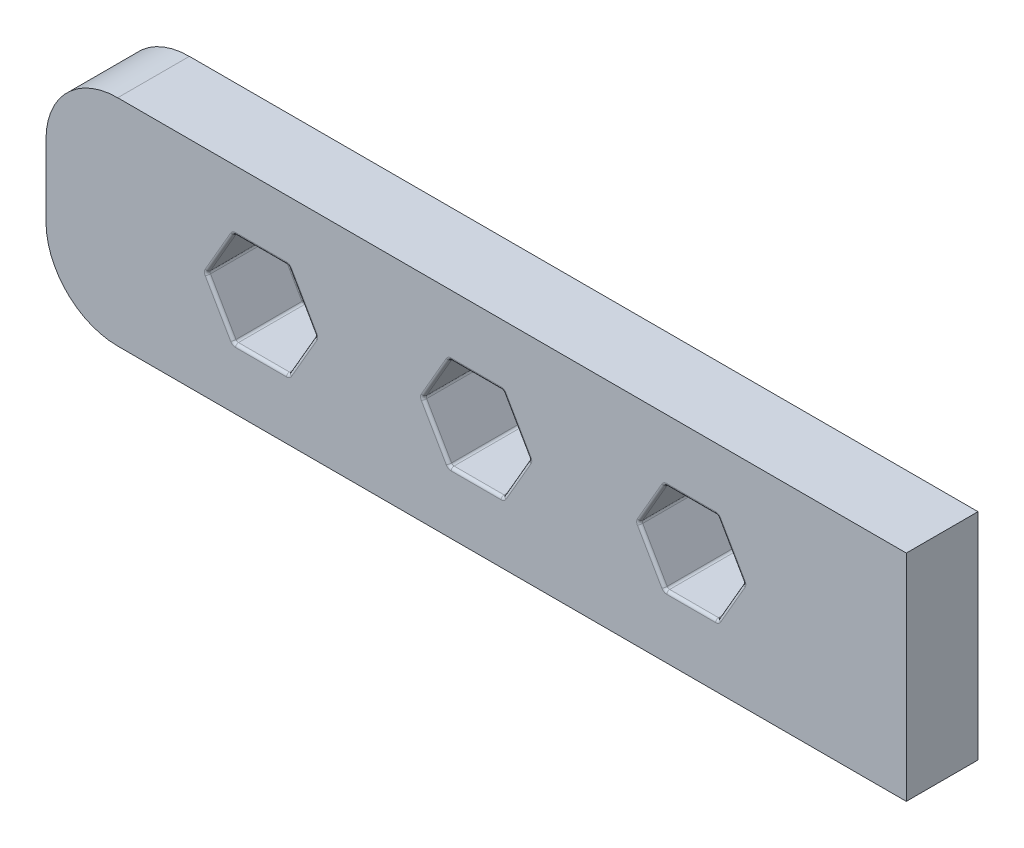
SolidWorks part; units mm, degrees
ref_plane "Front Plane" through (0, 0, 0) normal (0, 0, 1) x (1, 0, 0)
ref_plane "Top Plane" through (0, 0, 0) normal (0, 1, 0) x (1, 0, 0)
ref_plane "Right Plane" through (0, 0, 0) normal (1, 0, 0) x (0, 0, -1)
sketch "Sketch1" plane through (0, 0, 0) normal (0, 0, 1) x (1, 0, 0)
  line L1 (-25, -7.5) -> (30, -7.5)
  line L2 (-30, -2.5) -> (-30, 2.5)
  line L3 (-25, 7.5) -> (30, 7.5)
  line L4 (30, -7.5) -> (30, 7.5)
  line L5 (-30, -7.5) -> (30, 7.5) construction
  line L6 (-30, 7.5) -> (30, -7.5) construction
  arc A0 (-25, -7.5) -> (-30, -2.5) centre (-25, -2.5) cw
  arc A1 (-30, 2.5) -> (-25, 7.5) centre (-25, 2.5) cw
  point P0 (0, 0)
  dimension "D1" = 5
  dimension "D2" = 55
  dimension "D3" = 15
extrude "Boss-Extrude1" add sketch "Sketch1" along normal blind 5
sketch "Sketch2" plane through (0, 0, 0) normal (0, 0, 1) x (1, 0, 0)
  line L1 (-11.2184, 0) -> (-13.1092, 3.275)
  line L2 (-13.1092, 3.275) -> (-16.8908, 3.275)
  line L3 (-16.8908, 3.275) -> (-18.7816, 0)
  line L4 (-18.7816, 0) -> (-16.8908, -3.275)
  line L5 (-16.8908, -3.275) -> (-13.1092, -3.275)
  line L6 (-13.1092, -3.275) -> (-11.2184, 0)
  line L7 (3.7095, 0) -> (1.8547, 3.2125)
  line L8 (1.8547, 3.2125) -> (-1.8547, 3.2125)
  line L9 (-1.8547, 3.2125) -> (-3.7095, 0)
  line L10 (-3.7095, 0) -> (-1.8547, -3.2125)
  line L11 (-1.8547, -3.2125) -> (1.8547, -3.2125)
  line L12 (1.8547, -3.2125) -> (3.7095, 0)
  line L13 (18.6373, 0) -> (16.8187, 3.15)
  line L14 (16.8187, 3.15) -> (13.1813, 3.15)
  line L15 (13.1813, 3.15) -> (11.3627, 0)
  line L16 (11.3627, 0) -> (13.1813, -3.15)
  line L17 (13.1813, -3.15) -> (16.8187, -3.15)
  line L18 (16.8187, -3.15) -> (18.6373, 0)
  circle A0 centre (-15, 0) radius 3.275 construction
  circle A1 centre (0, 0) radius 3.2125 construction
  circle A2 centre (15, 0) radius 3.15 construction
  point P18 (0, 0)
  point P26 (45.4357, 0)
  dimension "D1" = 6.3
  dimension "D2" = 6.425
  dimension "D3" = 6.55
  dimension "D4" = 15
  dimension "D5" = 15
extrude "Cut-Extrude3" cut sketch "Sketch2" along normal blind 5
fillet "Fillet1" radius 0.2 54 edges at (15, 3.15, 5) (15, 3.15, 0) (17.728, -1.575, 5) (17.728, -1.575, 0) (12.272, -1.575, 5) (12.272, -1.575, 0) (0, 3.2125, 5) (0, 3.2125, 0) (2.7821, -1.6062, 5) (2.7821, -1.6062, 0) (-2.7821, -1.6062, 5) (-2.7821, -1.6062, 0) (-15, 3.275, 5) (-15, 3.275, 0) (-12.1638, -1.6375, 5) (-12.1638, -1.6375, 0) (-17.8362, -1.6375, 5) (-17.8362, -1.6375, 0) (11.3627, 0, 2.5) (12.272, 1.575, 5) (13.1813, 3.15, 2.5) (12.272, 1.575, 0) (16.8187, 3.15, 2.5) (17.728, 1.575, 5) (18.6373, 0, 2.5) (17.728, 1.575, 0) (16.8187, -3.15, 2.5) (15, -3.15, 5) (13.1813, -3.15, 2.5) (15, -3.15, 0) (-3.7095, 0, 2.5) (-2.7821, 1.6063, 5) (-1.8547, 3.2125, 2.5) (-2.7821, 1.6063, 0) (1.8547, 3.2125, 2.5) (2.7821, 1.6063, 5) (3.7095, 0, 2.5) (2.7821, 1.6063, 0) (1.8547, -3.2125, 2.5) (0, -3.2125, 5) (-1.8547, -3.2125, 2.5) (0, -3.2125, 0) (-18.7816, 0, 2.5) (-17.8362, 1.6375, 5) (-16.8908, 3.275, 2.5) (-17.8362, 1.6375, 0) (-13.1092, 3.275, 2.5) (-12.1638, 1.6375, 5) (-11.2184, 0, 2.5) (-12.1638, 1.6375, 0) (-13.1092, -3.275, 2.5) (-15, -3.275, 5) (-16.8908, -3.275, 2.5) (-15, -3.275, 0)
